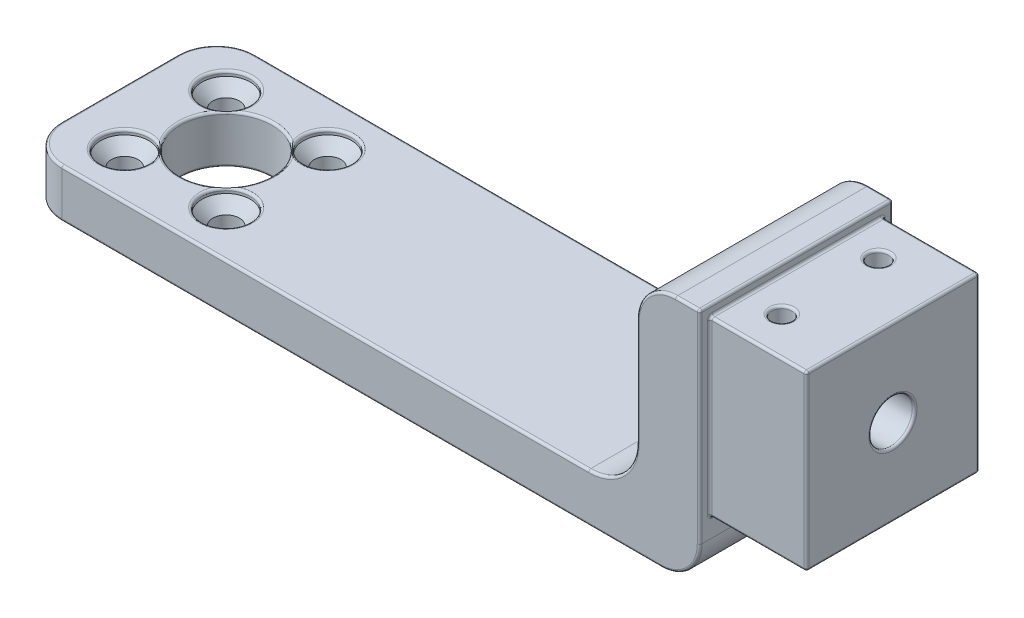
SolidWorks part; units mm, degrees
material "6061 Legierung"
ref_plane "Ebene vorne" through (0, 0, 0) normal (0, 0, 1) x (1, 0, 0)
ref_plane "Ebene oben" through (0, 0, 0) normal (0, 1, 0) x (1, 0, 0)
ref_plane "Ebene rechts" through (0, 0, 0) normal (1, 0, 0) x (0, 0, -1)
sketch "Skizze1" plane through (0, 0, 0) normal (0, 0, 1) x (1, 0, 0)
  line L0 (0, 0) -> (140, 0)
  line L1 (140, 0) -> (140, 12.1)
  line L2 (140, 12.1) -> (160, 12.1)
  line L3 (160, 12.1) -> (160, 47.9)
  line L4 (160, 47.9) -> (140, 47.9)
  line L5 (140, 47.9) -> (140, 50)
  line L6 (140, 50) -> (127, 50)
  line L7 (127, 50) -> (127, 10)
  line L8 (127, 10) -> (0, 10)
  line L9 (0, 10) -> (0, 0)
  dimension "D1" = 10
  dimension "D2" = 160
  dimension "D3" = 20
  dimension "D4" = 20
  dimension "D5" = 2.1
  dimension "D6" = 12.1
  dimension "D7" = 127
  dimension "D8" = 40
extrude "Aufsatz-Linear austragen1" add sketch "Skizze1" along normal blind 40
sketch "Skizze2" plane through (160, 0, 0) normal (1, 0, 0) x (0, 0, -1)
  line L1 (-37.9, 12.1) -> (-2.1, 12.1)
  line L2 (-37.9, 12.1) -> (-37.9, 47.9)
  line L3 (-37.9, 47.9) -> (-2.1, 47.9)
  line L4 (-2.1, 12.1) -> (-2.1, 47.9)
  line L5 (-40, 47.9) -> (0, 47.9) construction
  line L6 (-40, 12.1) -> (0, 12.1) construction
  line L7 (-48.6954, 8.7993) -> (6.3966, 8.7993)
  line L8 (-48.6954, 8.7993) -> (-48.6954, 50)
  line L9 (-48.6954, 50) -> (6.3966, 50)
  line L10 (6.3966, 8.7993) -> (6.3966, 50)
  line L11 (-20, 57.6527) -> (-20, -5.0002) construction
  line L12 (-40, 12.1) -> (-40, 47.9) construction
  dimension "D3" = 35.8
  dimension "D4" = 20
extrude "Schnitt-Linear austragen1" cut sketch "Skizze2" against normal up to surface (20 mm away) up to face at (140, 48.95, 20)
sketch "Skizze4" plane through (0, 0, 0) normal (0, -1, 0) x (1, 0, 0)
  line L0 (0, 40) -> (0, 0) construction
  line L1 (0, 0) -> (140, 0) construction
  circle A0 centre (22, 20) radius 9.5
  dimension "D1" = 19
  dimension "D2" = 22
  dimension "D3" = 20
extrude "Schnitt-Linear austragen2" cut sketch "Skizze4" against normal through all and the other way through all
hole_wizard "Formsenkung für M5 Linsensenkschraube mit Schlitz1" positions "Skizze5" profile "Skizze6" countersink size "M5" standard "DIN"
sketch "Skizze5" plane through (0, 10, 0) normal (0, 1, 0) x (1, 0, 0)
  line L3 (-6.2976, -20) -> (77.6135, -20) construction
  line L7 (22, -20) -> (22, -43.7547) construction
  line L10 (32.5, -9.5) -> (11.5, -9.5) construction
  line L11 (32.5, -9.5) -> (32.5, -30.5) construction
  line L12 (32.5, -30.5) -> (11.5, -30.5) construction
  line L13 (11.5, -9.5) -> (11.5, -30.5) construction
  line L14 (32.5, -9.5) -> (11.5, -30.5) construction
  line L15 (32.5, -30.5) -> (11.5, -9.5) construction
  point P0 (32.5, -30.5)
  point P2 (11.5, -30.5)
  point P4 (11.5, -9.5)
  point P6 (32.5, -9.5)
  dimension "D2" = 21
  dimension "D10" = 21
sketch "Skizze6" plane through (32.5, 10, 30.5) normal (1, 0, 0) x (0, 0, 1)
  line L0 (0, 0) -> (0, 18.7524)
  line L1 (0, 18.7524) -> (2.75, 17.1)
  line L2 (2.75, 17.1) -> (2.75, 3.25)
  line L3 (2.75, 3.25) -> (5, 1)
  line L4 (5, 1) -> (5, 0)
  line L6 (5, 0) -> (0, 0)
  line L7 (-2.75, 3.25) -> (-5, 1) construction
  line L10 (0, 18.7524) -> (-2.75, 17.1) construction
  line L11 (0, -6.35) -> (0, 107.95) construction
  dimension "Bohrerdurchmesser" = 5.5
  dimension "Bohrungstiefe" = 17.1
  dimension "Senkdurchmesser2" = 10
  dimension "Senkwinkel2" = 90
  dimension "Spitzenwinkel" = 118
  dimension "Kopfspielraum" = 1
fillet "Verrundung1" radius 8 4 edges at (140, 0, 20) (127, 50, 20) (0, 5, 0) (0, 5, 40)
hole_wizard "M5 Gewindebohrung1" positions "Skizze7" profile "Skizze9" tap size "M5" standard "ISO"
sketch "Skizze7" plane through (0, 47.9, 0) normal (0, 1, 0) x (1, 0, 0)
  line L0 (22, -20) -> (178.1184, -20) construction
  line L2 (140, -40) -> (140, 0) construction
  point P0 (147, -10)
  point P2 (147, -30)
  dimension "D1" = 20
  dimension "D2" = 7
sketch "Skizze9" plane through (147, 47.9, 10) normal (1, 0, 0) x (0, 0, 1)
  line L0 (0, 0) -> (0, 16.2618)
  line L1 (0, 16.2618) -> (2.1, 15)
  line L2 (2.1, 15) -> (2.1, 0)
  line L5 (2.1, 0) -> (0, 0)
  line L10 (0, 16.2618) -> (-2.1, 15) construction
  line L11 (0, -6.35) -> (0, 107.95) construction
  dimension "Bohrerdurchmesser" = 4.2
  dimension "Bohrungstiefe" = 15
  dimension "Spitzenwinkel" = 118
cosmetic thread "Bohrungsgewinde1" parameters "D1"=10, "D2"=5
cosmetic thread "Bohrungsgewinde2" parameters "D1"=10, "D2"=5
hole_wizard "M5 Gewindebohrung2" positions "Skizze10" profile "Skizze11" tap size "M5" standard "ISO"
sketch "Skizze10" plane through (0, 12.1, 0) normal (0, -1, 0) x (-1, 0, 0)
  line L0 (-140, -37.9) -> (-140, -2.1) construction
  line L1 (-22, -20) -> (-227.8808, -20) construction
  point P0 (-147, -10)
  point P2 (-147, -30)
  dimension "D1" = 20
  dimension "D2" = 7
sketch "Skizze11" plane through (147, 12.1, 10) normal (1, 0, 0) x (0, 0, -1)
  line L0 (0, 0) -> (0, 16.2618)
  line L1 (0, 16.2618) -> (2.1, 15)
  line L2 (2.1, 15) -> (2.1, 0)
  line L5 (2.1, 0) -> (0, 0)
  line L10 (0, 16.2618) -> (-2.1, 15) construction
  line L11 (0, -6.35) -> (0, 107.95) construction
  dimension "Bohrerdurchmesser" = 4.2
  dimension "Bohrungstiefe" = 15
  dimension "Spitzenwinkel" = 118
cosmetic thread "Bohrungsgewinde3" parameters "D1"=10, "D2"=5
cosmetic thread "Bohrungsgewinde4" parameters "D1"=10, "D2"=5
sketch "Skizze12" plane through (160, 0, 0) normal (1, 0, 0) x (0, 0, -1)
  circle A0 centre (-20, 30) radius 4.5
  dimension "D1" = 9
extrude "Schnitt-Linear austragen3" cut sketch "Skizze12" against normal up to next
fillet "Verrundung2" radius 10 1 edges at (127, 10, 20)
fillet "Verrundung3" radius 0.5 51 edges at (160, 30, 15.5) (160, 30, 2.1) (150, 47.9, 2.1) (160, 47.9, 20) (147, 47.9, 32.1) (147, 47.9, 12.1) (150, 47.9, 37.9) (160, 30, 37.9) (160, 12.1, 20) (150, 12.1, 2.1) (150, 12.1, 37.9) (147, 12.1, 27.9) (147, 12.1, 7.9) (140, 47.9, 20) (140, 30, 37.9) (140, 12.1, 20) (140, 30, 2.1) (2.3431, 0, 2.3431) (0, 0, 20) (2.3431, 0, 37.6569) (22, 0, 29.5) (32.5, 0, 12.25) (11.5, 0, 12.25) (11.5, 0, 33.25) (32.5, 0, 33.25) (140, 50, 20) (127, 30, 15.5) (2.3431, 10, 37.6569) (0, 10, 20) (2.3431, 10, 2.3431) (31.5, 10, 20) (32.5, 10, 14.5) (11.5, 10, 14.5) (11.5, 10, 35.5) (32.5, 10, 35.5) (137.5, 50, 0) (129.3431, 47.6569, 0) (127, 31, 0) (124.0711, 12.9289, 0) (62.5, 10, 0) (70, 0, 0) (137.6569, 2.3431, 0) (140, 29, 0) (62.5, 10, 40) (124.0711, 12.9289, 40) (127, 31, 40) (129.3431, 47.6569, 40) (137.5, 50, 40) (140, 29, 40) (137.6569, 2.3431, 40) (70, 0, 40)
